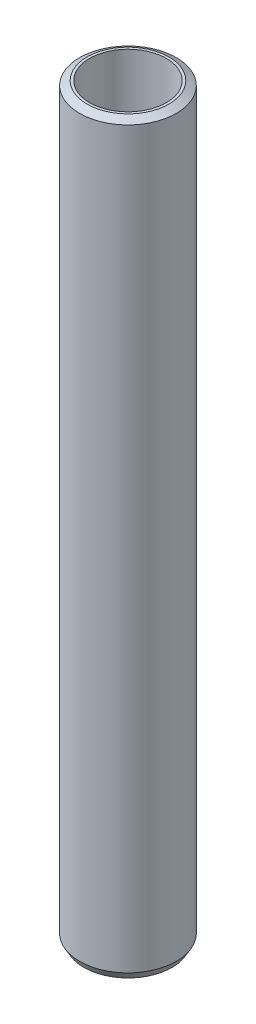
SolidWorks part; units mm, degrees
ref_plane "Front Plane" through (0, 0, 0) normal (0, 0, 1) x (1, 0, 0)
ref_plane "Top Plane" through (0, 0, 0) normal (0, 1, 0) x (1, 0, 0)
ref_plane "Right Plane" through (0, 0, 0) normal (1, 0, 0) x (0, 0, -1)
sketch "Sketch1" plane through (0, 0, 0) normal (0, 1, 0) x (1, 0, 0)
  circle A0 centre (0, 0) radius 35
  dimension "SHAFT_OD" = 70
extrude "Boss-Extrude1" add sketch "Sketch1" along normal blind 540.0112
sketch "Sketch2" plane through (0, 0, 0) normal (0, 1, 0) x (1, 0, 0)
  circle A0 centre (0, 0) radius 27.775
  dimension "BORE_D" = 55.55
extrude "Cut-Extrude1" cut sketch "Sketch2" along normal through all
chamfer "Chamfer1" distance 3.1122 angle 60.023 2 edges at (0, 540.0112, 35) (0, 0, 35) first distance on face at (0, 540.0112, 35) first distance on face at (0, 0, 27.775)
